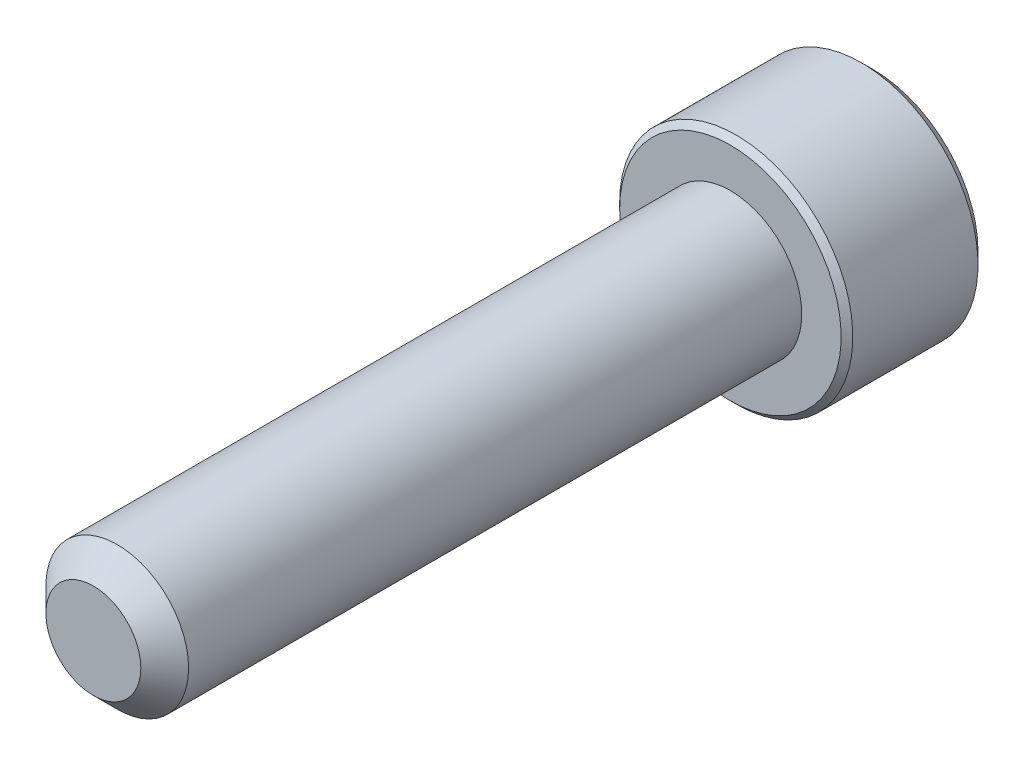
SolidWorks part; units mm, degrees
ref_plane "Front Plane" through (0, 0, 0) normal (0, 0, 1) x (1, 0, 0)
ref_plane "Top Plane" through (0, 0, 0) normal (0, 1, 0) x (1, 0, 0)
ref_plane "Right Plane" through (0, 0, 0) normal (1, 0, 0) x (0, 0, -1)
sketch "Sketch0" plane through (0, 0, 0) normal (1, 0, 0) x (0, 0, -1)
  line L0 (0, 0) -> (12.7, 0) construction
  point P2 (15.5448, 0)
  point P4 (0, 0)
  dimension "D1" = 12.7
  dimension "D2" = 2.8448
  dimension "Min Thread" = 0
sketch "Sketch1" plane through (0, 0, 0) normal (0, 0, 1) x (1, 0, 0)
  circle A0 centre (0, 0) radius 1.4224
  dimension "OD" = 2.8448
extrude "Extrude1" add sketch "Sketch1" against normal blind 12.7
sketch "Sketch2" plane through (0, 0, 0) normal (0, 0, 1) x (1, 0, 0)
  circle A0 centre (0, 0) radius 1.4224 construction
  circle A1 centre (0, 0) radius 1.4224
curve "Helix/Spiral1" pitch 0.635 height 13.335 turns 21 parameters "pitch"=0.635
chamfer "Chamfer3" distance 0.4763 angle 45 1 edges at (1.4224, 0, 0)
sketch "Sketch3" plane through (0, 0, 0) normal (1, 0, 0) x (0, 0, -1)
  line L0 (-0.5556, 1.4224) -> (-0.3175, 1.01)
  line L1 (-0.3175, 1.01) -> (-0.2381, 1.01)
  line L2 (-0.2381, 1.01) -> (0, 1.4224)
  line L3 (-0.5556, 1.4224) -> (0, 1.4224)
  line L4 (-0.2778, 1.4224) -> (-0.2778, 1.01) construction
  line L5 (-0.4366, 1.2162) -> (-0.1191, 1.2162) construction
  line L6 (0, 1.4224) -> (0, -1.4224) construction
  dimension "D1" = 0.0794
  dimension "D2" = 0.3175
  dimension "D3" = 60
sweep "Cut-Sweep1" [suppressed] cut profiles "Sketch3" path "Helix/Spiral1"
sketch "Sketch5" [suppressed] plane through (0, 0, 0) normal (1, 0, 0) x (0, 0, -1)
  line L0 (12.7, -1.0232) -> (12.7, 1.0149) construction
  line L1 (12.7, 1.4224) -> (0, 1.4224)
  line L2 (12.7, 1.4224) -> (12.7, 0)
  line L3 (12.7, 0) -> (-0.5177, 0)
  line L4 (0, 0) -> (12.7, 0) construction
  line L5 (0, 1.4224) -> (-0.5177, 0)
  line L6 (0, 0) -> (15.24, 0) construction
  dimension "D1" = 70
  dimension "D3" = 2.54
revolve "partially thread" [suppressed] add sketch "Sketch5" angle 360 about L6
sketch "Sketch6" plane through (0, 0, -12.7) normal (0, 0, -1) x (-1, 0, 0)
  circle A0 centre (0, 0) radius 2.3241
  dimension "head dia" = 4.6482
extrude "Extrude2" add sketch "Sketch6" along normal blind 2.8448
sketch "Sketch7" plane through (0, 0, -15.5448) normal (0, 0, -1) x (-1, 0, 0)
  line L1 (0, 1.3748) -> (-1.1906, 0.6874)
  line L2 (-1.1906, 0.6874) -> (-1.1906, -0.6874)
  line L3 (-1.1906, -0.6874) -> (0, -1.3748)
  line L4 (0, -1.3748) -> (1.1906, -0.6874)
  line L5 (1.1906, -0.6874) -> (1.1906, 0.6874)
  line L6 (1.1906, 0.6874) -> (0, 1.3748)
  circle A0 centre (0, 0) radius 1.1906 construction
  dimension "hex dia" = 2.3813
extrude "Cut-Extrude1" cut sketch "Sketch7" against normal blind 1.7859
sketch "Sketch8" plane through (0, 0, -15.5448) normal (0, 0, -1) x (-1, 0, 0)
  circle A0 centre (0, 0) radius 1.3748
extrude "Cut-Extrude2" cut sketch "Sketch8" against normal through all draft 45
chamfer "Chamfer1" distance 0.2324 angle 45 1 edges at (-2.3241, 0, -15.5448)
chamfer "Chamfer2" distance 0.1162 angle 45 1 edges at (-2.3241, 0, -12.7)
sketch "Sketch9" plane through (0, 0, 0) normal (1, 0, 0) x (0, 0, -1)
  line L0 (0, 1.4224) -> (0, -1.4224) construction
  line L1 (1.5875, 1.4224) -> (1.5875, -1.4224) construction
  line L2 (15.5448, 2.3241) -> (15.5448, -2.3241) construction
  line L3 (12.7, 2.3241) -> (12.7, -2.3241) construction
  line L4 (12.7, 2.2079) -> (12.7, -2.2079) construction
  line L5 (15.5448, -2.0917) -> (15.5448, 2.0917) construction
  line L6 (12.7, -2.3241) -> (12.7, 2.3241) construction
  line L7 (0, 0.9462) -> (0, -0.9462) construction
  line L8 (-0.5556, 1.4224) -> (0, 1.4224) construction
  line L9 (1.5875, 0) -> (0, 0) construction
  dimension "D1" = 1.5875
equation "\"D3@Helix/Spiral1\" = \"screw length@Extrude1\"+\"pitch@Helix/Spiral1\""
equation "\"D1@Sketch3\" = \"pitch@Helix/Spiral1\"*.125"
equation "\"D2@Sketch3\" = \"pitch@Helix/Spiral1\"*.5"
equation "\"D1@Cut-Extrude1\" = \"hex dia@Sketch7\"*.75"
equation "\"D1@Chamfer1\" = \"head dia@Sketch6\"*.05"
equation "\"D1@Sketch9\" = \"pitch@Helix/Spiral1\"*2.50"
equation "\"D1@Chamfer2\" = \"D1@Chamfer1\"/2"
equation "\"D1@Chamfer3\" = \"pitch@Helix/Spiral1\"*.750"
equation "\"D1@Sketch0\" = \"screw length@Extrude1\""
equation "\"D2@Sketch0\" = \"head depth@Extrude2\""
